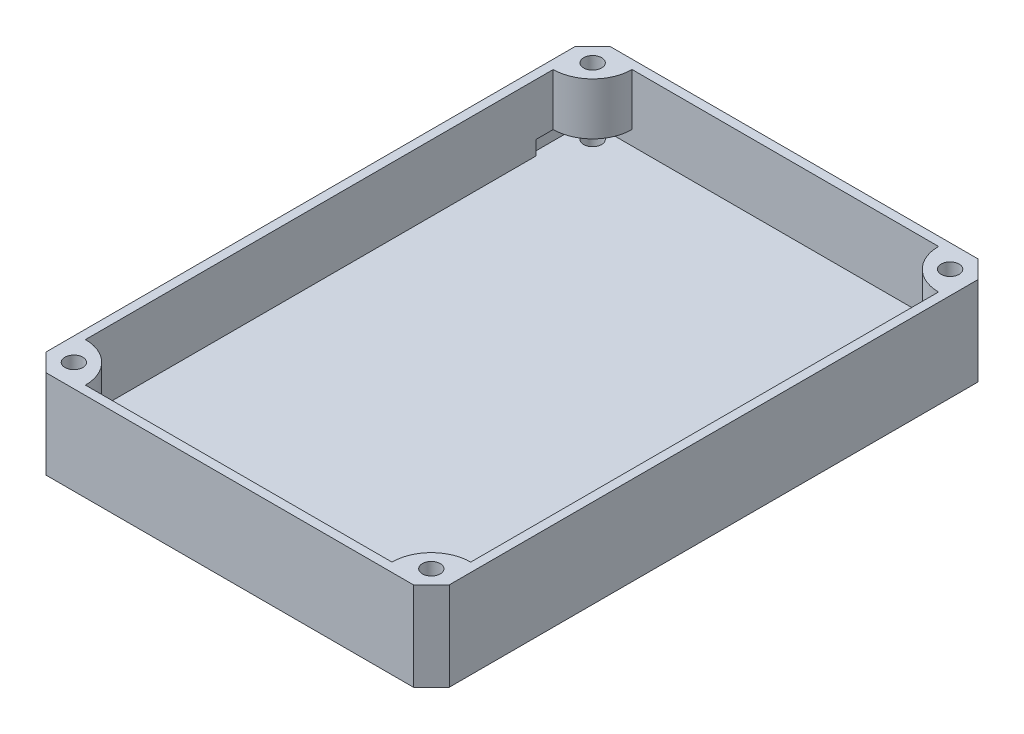
SolidWorks part; units mm, degrees
ref_plane "Front Plane" through (0, 0, 0) normal (0, 0, 1) x (1, 0, 0)
ref_plane "Top Plane" through (0, 0, 0) normal (0, 1, 0) x (1, 0, 0)
ref_plane "Right Plane" through (0, 0, 0) normal (1, 0, 0) x (0, 0, -1)
sketch "Sketch1" plane through (0, 0, 0) normal (0, 1, 0) x (1, 0, 0)
  line L1 (22.5, -31.5) -> (-22.5, -31.5)
  line L2 (22.5, -31.5) -> (22.5, 31.5)
  line L3 (22.5, 31.5) -> (-22.5, 31.5)
  line L4 (-22.5, -31.5) -> (-22.5, 31.5)
  line L5 (22.5, -31.5) -> (-22.5, 31.5) construction
  line L6 (22.5, 31.5) -> (-22.5, -31.5) construction
  line L7 (21.5, -30.5) -> (-21.5, -30.5)
  line L8 (21.5, -30.5) -> (21.5, 30.5)
  line L9 (21.5, 30.5) -> (-21.5, 30.5)
  line L10 (-21.5, -30.5) -> (-21.5, 30.5)
  line L11 (21.5, -30.5) -> (-21.5, 30.5) construction
  line L12 (21.5, 30.5) -> (-21.5, -30.5) construction
  point P0 (0, 0)
  point P6 (0, 0)
  dimension "D1" = 45
  dimension "D2" = 63
  dimension "D3" = 1
  dimension "D4" = 1
extrude "Boss-Extrude1" add sketch "Sketch1" along normal blind 7.4
sketch "Sketch2" plane through (0, 0, 0) normal (0, -1, 0) x (1, 0, 0)
  line L1 (-22.5, 31.5) -> (22.5, 31.5)
  line L2 (-22.5, 31.5) -> (-22.5, -31.5)
  line L3 (-22.5, -31.5) -> (22.5, -31.5)
  line L4 (22.5, 31.5) -> (22.5, -31.5)
  line L5 (-22.5, 31.5) -> (22.5, -31.5) construction
  line L6 (-22.5, -31.5) -> (22.5, 31.5) construction
  point P4 (0, 0)
extrude "Boss-Extrude2" add sketch "Sketch2" along normal blind 2.5
sketch "Sketch3" plane through (0, 0, 0) normal (0, 1, 0) x (1, 0, 0)
  line L0 (0, 31.5) -> (0, -31.5) construction
  line L1 (22.5, 31.5) -> (-22.5, 31.5) construction
  line L2 (-22.5, -31.5) -> (22.5, -31.5) construction
  line L3 (-21.5, 26.1) -> (-21.5, 30.5)
  line L4 (22.5, -31.5) -> (22.5, 31.5) construction
  line L5 (22.5, 0) -> (-22.5, 0) construction
  line L6 (-22.5, 31.5) -> (-22.5, -31.5) construction
  line L7 (-21.5, 30.5) -> (-21.5, -30.5) construction
  line L8 (21.5, 30.5) -> (-21.5, 30.5) construction
  line L9 (-21.5, 30.5) -> (-18.3887, 27.3887) construction
  line L10 (-21.5, 30.5) -> (-17.1, 30.5)
  line L11 (-21.5, 30.5) -> (-21.5, 26.1)
  line L12 (-17.1, 30.5) -> (-21.5, 30.5)
  line L13 (-21.5, 26.1) -> (-21.5, 30.5)
  line L14 (-21.5, 30.5) -> (-17.1, 30.5)
  line L15 (-21.5, 30.5) -> (-21.5, 26.1)
  line L16 (-17.1, 30.5) -> (-21.5, 30.5)
  line L17 (-21.5, 26.1) -> (-21.5, 30.5)
  line L18 (-21.5, 30.5) -> (-17.1, 30.5)
  line L19 (-21.5, 30.5) -> (-21.5, 26.1)
  line L20 (-17.1, 30.5) -> (-21.5, 30.5)
  line L21 (-21.5, 26.1) -> (-21.5, 30.5)
  line L22 (-21.5, 30.5) -> (-17.1, 30.5)
  line L23 (-21.5, 30.5) -> (-21.5, 26.1)
  line L24 (-17.1, 30.5) -> (-21.5, 30.5)
  line L25 (21.5, 30.5) -> (18.3887, 27.3887) construction
  line L26 (17.1, 30.5) -> (21.5, 30.5)
  line L27 (21.5, 30.5) -> (21.5, 26.1)
  line L28 (21.5, 30.5) -> (17.1, 30.5)
  line L29 (21.5, 26.1) -> (21.5, 30.5)
  line L30 (17.1, 30.5) -> (21.5, 30.5)
  line L31 (21.5, 30.5) -> (21.5, 26.1)
  line L32 (21.5, 30.5) -> (17.1, 30.5)
  line L33 (21.5, 26.1) -> (21.5, 30.5)
  line L34 (17.1, 30.5) -> (21.5, 30.5)
  line L35 (21.5, 30.5) -> (21.5, 26.1)
  line L36 (21.5, 30.5) -> (17.1, 30.5)
  line L37 (21.5, 26.1) -> (21.5, 30.5)
  line L38 (17.1, 30.5) -> (21.5, 30.5)
  line L39 (21.5, 30.5) -> (21.5, 26.1)
  line L40 (21.5, 30.5) -> (17.1, 30.5)
  line L41 (21.5, 26.1) -> (21.5, 30.5)
  line L42 (21.5, -30.5) -> (18.3887, -27.3887) construction
  line L43 (-21.5, -30.5) -> (-18.3887, -27.3887) construction
  line L44 (21.5, -26.1) -> (21.5, -30.5)
  line L45 (21.5, -30.5) -> (17.1, -30.5)
  line L46 (21.5, -30.5) -> (21.5, -26.1)
  line L47 (17.1, -30.5) -> (21.5, -30.5)
  line L48 (21.5, -26.1) -> (21.5, -30.5)
  line L49 (21.5, -30.5) -> (17.1, -30.5)
  line L50 (21.5, -30.5) -> (21.5, -26.1)
  line L51 (17.1, -30.5) -> (21.5, -30.5)
  line L52 (21.5, -26.1) -> (21.5, -30.5)
  line L53 (21.5, -30.5) -> (17.1, -30.5)
  line L54 (21.5, -30.5) -> (21.5, -26.1)
  line L55 (17.1, -30.5) -> (21.5, -30.5)
  line L56 (21.5, -26.1) -> (21.5, -30.5)
  line L57 (21.5, -30.5) -> (17.1, -30.5)
  line L58 (21.5, -30.5) -> (21.5, -26.1)
  line L59 (17.1, -30.5) -> (21.5, -30.5)
  line L60 (-17.1, -30.5) -> (-21.5, -30.5)
  line L61 (-21.5, -30.5) -> (-21.5, -26.1)
  line L62 (-21.5, -30.5) -> (-17.1, -30.5)
  line L63 (-21.5, -26.1) -> (-21.5, -30.5)
  line L64 (-17.1, -30.5) -> (-21.5, -30.5)
  line L65 (-21.5, -30.5) -> (-21.5, -26.1)
  line L66 (-21.5, -30.5) -> (-17.1, -30.5)
  line L67 (-21.5, -26.1) -> (-21.5, -30.5)
  line L68 (-17.1, -30.5) -> (-21.5, -30.5)
  line L69 (-21.5, -30.5) -> (-21.5, -26.1)
  line L70 (-21.5, -30.5) -> (-17.1, -30.5)
  line L71 (-21.5, -26.1) -> (-21.5, -30.5)
  line L72 (-17.1, -30.5) -> (-21.5, -30.5)
  line L73 (-21.5, -30.5) -> (-21.5, -26.1)
  line L74 (-21.5, -30.5) -> (-17.1, -30.5)
  line L75 (-21.5, -26.1) -> (-21.5, -30.5)
  arc A0 (-21.5, 26.1) -> (-17.1, 30.5) centre (-21.5, 30.5) ccw
  circle A1 centre (-19.9444, 28.9444) radius 1
  circle A3 centre (19.9444, 28.9444) radius 1
  arc A4 (21.5, 26.1) -> (17.1, 30.5) centre (21.5, 30.5) cw
  arc A7 (21.5, -26.1) -> (17.1, -30.5) centre (21.5, -30.5) ccw
  circle A8 centre (19.9444, -28.9444) radius 1
  circle A9 centre (-19.9444, -28.9444) radius 1
  arc A10 (-21.5, -26.1) -> (-17.1, -30.5) centre (-21.5, -30.5) cw
  line M3 (21.5, 30.5) -> (-21.5, 30.5)
  line M4 (-21.5, 30.5) -> (-21.5, -30.5)
  line M5 (-21.5, -30.5) -> (21.5, -30.5)
  line M6 (21.5, -30.5) -> (21.5, 30.5)
  dimension "D2" = 2
  dimension "D1" = 2.2
extrude "Boss-Extrude3" add sketch "Sketch3" along normal up to surface (7.4 mm away) contours A0 A1 M4 M3 | A4 A3 M6 M3 | A7 A8 M6 M5 | A10 A9 M4 M5 region at (-21.4378, 0, -28.3) region at (-18.4327, 0, 27.4327) region at (19.3, 0, -30.4378) region at (18.4327, 0, 27.4327) up to face at (0, 7.4, 0)
sketch "Sketch4" plane through (0, 0, -31.5) normal (0, 0, -1) x (-1, 0, 0)
  line L0 (0, -2.5) -> (0, 12.3379) construction
  line L1 (-10.5, -1.5) -> (-13.5, -1.5)
  line L2 (-10.5, -1.5) -> (-10.5, 8.5)
  line L3 (-10.5, 8.5) -> (-13.5, 8.5)
  line L4 (-13.5, -1.5) -> (-13.5, 8.5)
  line L5 (-10.5, -1.5) -> (-13.5, 8.5) construction
  line L6 (-10.5, 8.5) -> (-13.5, -1.5) construction
  line L7 (22.5, -2.5) -> (-22.5, -2.5) construction
  point P4 (-12, 3.5)
  dimension "D1" = 12
  dimension "D2" = 10
  dimension "D3" = 3
  dimension "D4" = 6
extrude "Boss-Extrude4" [suppressed] add sketch "Sketch4" along normal blind 10
sketch "Sketch5" [suppressed] plane through (10.5, 0, 0) normal (-1, 0, 0) x (0, 0, 1)
  line L0 (-42, -0.2) -> (-42, 9.8) construction
  line L1 (-42, -0.2) -> (-32, -0.2) construction
  circle A0 centre (-39, 3.3) radius 1
  dimension "D3" = 2
  dimension "D1" = 3
  dimension "D2" = 3.5
extrude "Cut-Extrude1" [suppressed] cut sketch "Sketch5" against normal blind 1 contours A0
chamfer "Chamfer3" [suppressed] distance 5 angle 70
fillet "Fillet4" [suppressed] radius 2
mirror "Mirror8" [suppressed] about plane through (0, 0, 0) normal (1, 0, 0)
mirror "Mirror9" [suppressed] about plane through (0, 0, 0) normal (0, 0, 1)
sketch "Sketch6" plane through (-21.5, 0, 0) normal (1, 0, 0) x (0, 0, -1)
  line L0 (26.1, 3.2) -> (-26.1, 3.2) construction
  line L1 (19.9211, 1.2) -> (16.9211, 1.2)
  line L2 (19.9211, 1.2) -> (19.9211, 3.2)
  line L3 (19.9211, 3.2) -> (16.9211, 3.2)
  line L4 (16.9211, 1.2) -> (16.9211, 3.2)
  line L5 (19.9211, 1.2) -> (16.9211, 3.2) construction
  line L6 (19.9211, 3.2) -> (16.9211, 1.2) construction
  line L7 (1.5, 1.2) -> (-1.5, 1.2)
  line L8 (1.5, 1.2) -> (1.5, 3.2)
  line L9 (1.5, 3.2) -> (-1.5, 3.2)
  line L10 (-1.5, 1.2) -> (-1.5, 3.2)
  line L11 (1.5, 1.2) -> (-1.5, 3.2) construction
  line L12 (1.5, 3.2) -> (-1.5, 1.2) construction
  line L13 (-16.9211, 1.2) -> (-19.9211, 1.2)
  line L14 (-16.9211, 1.2) -> (-16.9211, 3.2)
  line L15 (-16.9211, 3.2) -> (-19.9211, 3.2)
  line L16 (-19.9211, 1.2) -> (-19.9211, 3.2)
  line L17 (-16.9211, 1.2) -> (-19.9211, 3.2) construction
  line L18 (-16.9211, 3.2) -> (-19.9211, 1.2) construction
  line L19 (26.1, 0) -> (-26.1, 0) construction
  line L20 (-26.1, 7.4) -> (-26.1, 0) construction
  line L21 (26.1, 7.4) -> (26.1, 0) construction
  line L22 (0, 3.2) -> (0, 1.2) construction
  line L23 (-18.4211, 2.2) -> (0, 2.2) construction
  line L24 (0, 2.2) -> (18.4211, 2.2) construction
  point P5 (18.4211, 2.2)
  point P9 (0, 2.2)
  point P14 (-18.4211, 2.2)
  point P28 (0, 3.2)
  dimension "D1" = 3.2
  dimension "D2" = 3
  dimension "D3" = 2
sketch "Sketch7" plane through (0, 0, 0) normal (0, 1, 0) x (1, 0, 0)
  line L0 (0, 31.5) -> (0, 15.0341) construction
  line L1 (22.5, 31.5) -> (-22.5, 31.5) construction
  line L3 (21, 30.5) -> (-21, 30.5)
  line L5 (22, 24.2016) -> (-22, 24.2016)
  line L6 (-22, 29.5) -> (-22, 24.2016)
  line L7 (0, 30.5) -> (-22, 24.2016) construction
  line L8 (17.1, 30.5) -> (-17.1, 30.5) construction
  line L9 (-21.5, 26.1) -> (-21.5, -26.1) construction
  line L11 (0, 30.5) -> (22, 24.2016) construction
  line L12 (22, 29.5) -> (22, 24.2016)
  arc A0 (21, 30.5) -> (22, 29.5) centre (21, 29.5) cw
  arc A1 (-22, 29.5) -> (-21, 30.5) centre (-21, 29.5) cw
  point P8 (-9.217, 27.8613)
  point P15 (9.217, 27.8613)
  dimension "D3" = 1
  dimension "D2" = 0.5
  dimension "D4" = 6.2984
extrude "Cut-Extrude3" cut sketch "Sketch7" along normal blind 1.6
extrude "Cut-Extrude7" cut sketch "Sketch3<5>" against normal blind 10 contours A9 | A8 | A3 | A1 region at (-19.9444, 0, -28.9444) region at (19.9444, 0, -28.9444) region at (19.9444, 0, 28.9444) region at (-19.9444, 0, 28.9444)
sketch "Sketch3<5>" plane through (0, 0, 0) normal (0, 1, 0) x (1, 0, 0) same geometry as "Sketch3"
sketch "Sketch10" plane through (0, -2.5, 0) normal (0, -1, 0) x (1, 0, 0)
  circle A0 centre (-19.9444, 28.9444) radius 2
  circle A1 centre (19.9444, 28.9444) radius 2
  circle A2 centre (19.9444, -28.9444) radius 2
  circle A3 centre (-19.9444, -28.9444) radius 2
  dimension "D1" = 4
extrude "Cut-Extrude10" [suppressed] cut sketch "Sketch10" against normal blind 2
chamfer "Chamfer4" distance 2 angle 45 4 edges at (-22.5, 2.45, 31.5) (22.5, 2.45, 31.5) (22.5, 2.45, -31.5) (-22.5, 2.45, -31.5)
chamfer "Chamfer5" distance 0.6 angle 45 4 edges at (19.9444, -2.5, 27.9444) (-19.9444, -2.5, 27.9444) (-19.9444, -2.5, -29.9444) (19.9444, -2.5, -29.9444)
